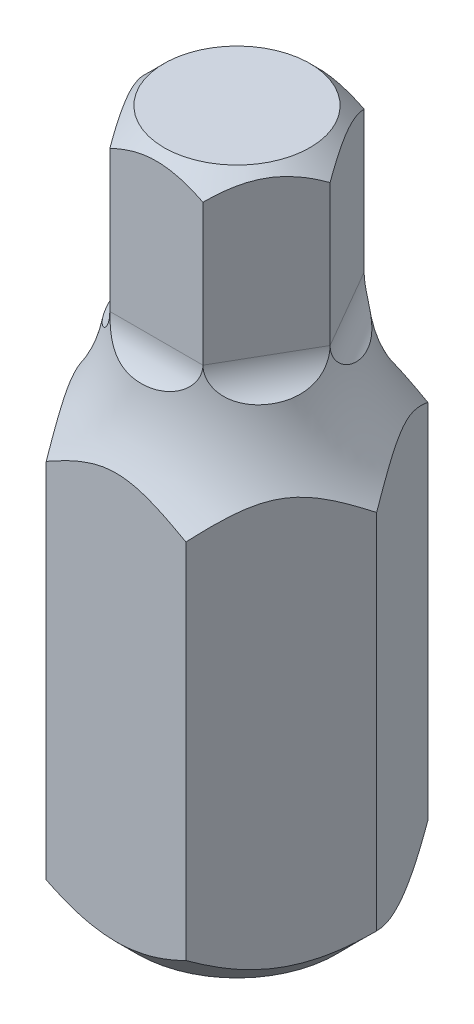
SolidWorks part; units mm, degrees
material "Stainless Steel (ferritic)"
ref_plane "Front Plane" through (0, 0, 0) normal (0, 0, 1) x (1, 0, 0)
ref_plane "Top Plane" through (0, 0, 0) normal (0, 1, 0) x (1, 0, 0)
ref_plane "Right Plane" through (0, 0, 0) normal (1, 0, 0) x (0, 0, -1)
sketch "Sketch1" plane through (0, 0, 0) normal (0, 1, 0) x (1, 0, 0)
  line L0 (-1.7321, 3) -> (1.7321, 3)
  line L1 (1.7321, 3) -> (3.4641, 0)
  line L2 (3.4641, 0) -> (1.7321, -3)
  line L3 (1.7321, -3) -> (-1.7321, -3)
  line L4 (-1.7321, -3) -> (-3.4641, 0)
  line L5 (-3.4641, 0) -> (-1.7321, 3)
  line L6 (-2.3094, 0) -> (-1.1547, 2)
  line L7 (-1.1547, 2) -> (1.1547, 2)
  line L8 (1.1547, 2) -> (2.3094, 0)
  line L9 (2.3094, 0) -> (1.1547, -2)
  line L10 (1.1547, -2) -> (-1.1547, -2)
  line L11 (-1.1547, -2) -> (-2.3094, 0)
  circle A0 centre (0, 0) radius 3
  dimension "D1" = 120
  dimension "D2" = 120
  dimension "D3" = 6
  dimension "D4" = 1
extrude "Boss-Extrude1" add sketch "Sketch1" along normal blind 12 contours A0 L1 L0 | A0 L10 L11 L6 L7 L8 L9 | A0 L0 L5 | A0 L5 L4 | A0 L4 L3 | A0 L3 L2 | A0 L2 L1 | L11 L10 L9 L8 L7 L6 region at (-1.5503, 0, -2.6853) region at (1.5503, 0, -2.6853) region at (1.4576, 0, -2.5246) region at (-3.1007, 0, 0) region at (3.1007, 0, 0) region at (-1.5503, 0, 2.6853) region at (1.5503, 0, 2.6853) region at (0, 0, 0)
extrude "Boss-Extrude2" add sketch "Sketch1<3>" along normal blind 5 from surface contours L11 L10 L9 L8 L7 L6 region at (0, 0, 0) starting at face at (0, 12, 0)
sketch "Sketch1<3>" plane through (0, 0, 0) normal (0, 1, 0) x (1, 0, 0) same geometry as "Sketch1"
ref_plane "Plane1" through (0, 0, 0) normal (0.866, 0, -0.5) x (-0.5, 0, -0.866)
fillet "Fillet1" radius 1 6 edges at (0, 12, -2) (1.7321, 12, -1) (1.7321, 12, 1) (0, 12, 2) (-1.7321, 12, 1) (-1.7321, 12, -1)
sketch "Sketch2" plane through (0, 0, 0) normal (-0.866, 0, 0.5) x (0.5, 0, 0.866)
  line L0 (-2.3094, 13) -> (-4, 13)
  line L1 (-4, 13) -> (-4, 9.4847)
  line L2 (-3.4641, 12) -> (-3.4641, 0) construction
  line L3 (-2.3094, 13) -> (-2.3094, 9.4847) construction
  line L4 (-2.3094, 9.4847) -> (-4, 9.4847) construction
  line L5 (-4, 0) -> (-4, 1.5359)
  line L6 (-4, 1.5359) -> (-2.4641, 0)
  line L8 (-2.4641, 0) -> (-4, 0)
  line L9 (-1.8094, 17) -> (-4, 14.8094)
  line L10 (2.3094, 17) -> (1.1547, 17) construction
  line L11 (-1.7321, 0) -> (-3.4641, 0) construction
  line L12 (-4, 14.8094) -> (-4, 17)
  line L13 (-4, 17) -> (-1.8094, 17)
  line L14 (0, 17) -> (0, 0) construction
  line L18 (-2.3094, 17) -> (-2.3094, 13) construction
  line L19 (-2.3094, 13) -> (-1.1547, 13) construction
  arc A0 (-4, 9.4847) -> (-2.3094, 13) centre (-6.8094, 13) ccw
  point P35 (-3.4641, 9.9902)
  dimension "4.5" = 4.5
  dimension "D1" = 0.5
  dimension "D2" = 1
  dimension "D4" = 8
revolve "Cut-Revolve2" cut sketch "Sketch2" angle 360 about L14
equation "\"A\"= 6mm"
equation "\"D3@Sketch1\"=\"A\""
